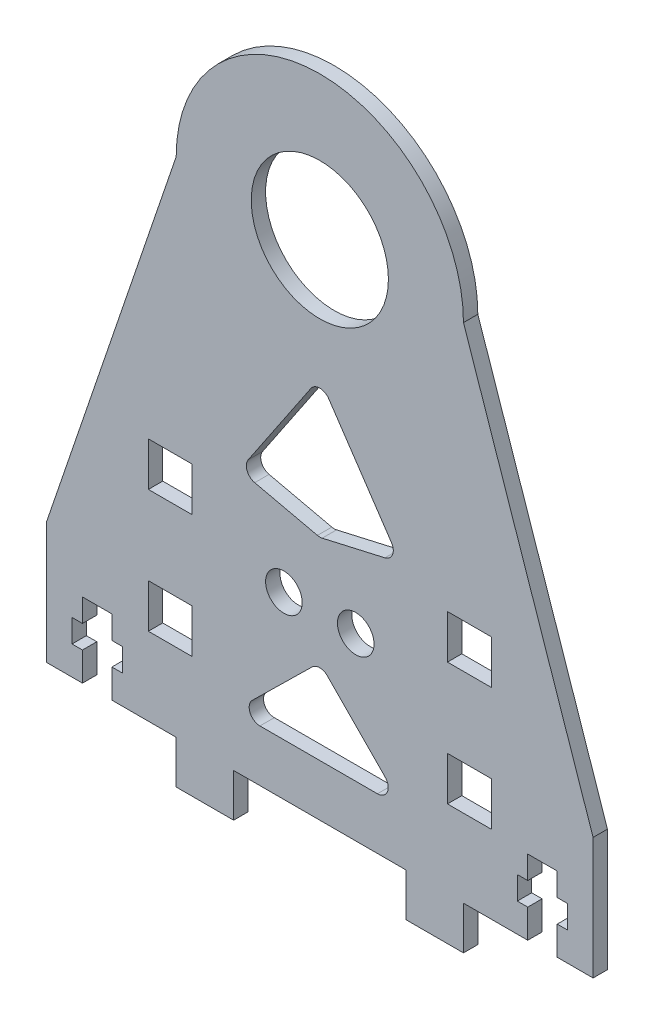
SolidWorks part; units mm, degrees
ref_plane "前视基准面" through (0, 0, 0) normal (0, 0, 1) x (1, 0, 0)
ref_plane "上视基准面" through (0, 0, 0) normal (0, 1, 0) x (1, 0, 0)
ref_plane "右视基准面" through (0, 0, 0) normal (1, 0, 0) x (0, 0, -1)
sketch "草图1" plane through (0, 0, 0) normal (0, 0, 1) x (1, 0, 0)
  line L0 (-30.7912, 3.1303) -> (31.2088, 3.1303) construction
  line L1 (-30.7912, 3.1303) -> (-30.7912, 5.1553) construction
  line L2 (-28.7412, 3.1303) -> (-28.7412, 7.1303)
  line L3 (-28.7412, 7.1303) -> (-27.2912, 7.1303)
  line L4 (-27.2912, 7.1303) -> (-27.2912, 10.3303)
  line L5 (-27.2912, 10.3303) -> (-28.7412, 10.3303)
  line L6 (-28.7412, 10.3303) -> (-28.7412, 13.5303)
  line L7 (-28.7412, 13.5303) -> (-32.8412, 13.5303)
  line L8 (-34.2912, 7.1303) -> (-34.2912, 10.3303)
  line L9 (-32.8412, 10.3303) -> (-32.8412, 13.5303)
  line L10 (-32.8412, 3.1303) -> (-32.8412, 7.1303)
  line L11 (-32.8412, 7.1303) -> (-34.2912, 7.1303)
  line L12 (-34.2912, 10.3303) -> (-32.8412, 10.3303)
  line L13 (-32.8412, 3.1303) -> (-37.8412, 3.1303)
  line L14 (-37.8412, 3.1303) -> (-37.8412, 93.1303) construction
  line L15 (-19.7912, 3.1303) -> (-19.7912, -2.8697)
  line L16 (-19.7912, -2.8697) -> (-11.7912, -2.8697)
  line L17 (-11.7912, -2.8697) -> (-11.7912, 3.1303)
  line L18 (-15.7912, -2.8697) -> (-15.7912, 3.1303) construction
  line L19 (-28.7412, 3.1303) -> (-19.7912, 3.1303)
  line L20 (0.2088, 3.1303) -> (0.2088, -7.8241) construction
  line L21 (-11.7912, 3.1303) -> (12.2088, 3.1303)
  line L22 (16.2088, -2.8697) -> (16.2088, 3.1303) construction
  line L23 (31.2088, 3.1303) -> (31.2088, 5.1553) construction
  line L24 (29.1588, 3.1303) -> (20.2088, 3.1303)
  line L25 (12.2088, -2.8697) -> (12.2088, 3.1303)
  line L26 (20.2088, -2.8697) -> (12.2088, -2.8697)
  line L27 (20.2088, 3.1303) -> (20.2088, -2.8697)
  line L28 (38.2588, 3.1303) -> (38.2588, 93.1303) construction
  line L29 (33.2588, 3.1303) -> (38.2588, 3.1303)
  line L30 (34.7088, 10.3303) -> (33.2588, 10.3303)
  line L31 (33.2588, 7.1303) -> (34.7088, 7.1303)
  line L32 (33.2588, 3.1303) -> (33.2588, 7.1303)
  line L33 (33.2588, 10.3303) -> (33.2588, 13.5303)
  line L34 (34.7088, 7.1303) -> (34.7088, 10.3303)
  line L35 (29.1588, 13.5303) -> (33.2588, 13.5303)
  line L36 (29.1588, 10.3303) -> (29.1588, 13.5303)
  line L37 (27.7088, 10.3303) -> (29.1588, 10.3303)
  line L38 (27.7088, 7.1303) -> (27.7088, 10.3303)
  line L39 (29.1588, 7.1303) -> (27.7088, 7.1303)
  line L40 (29.1588, 3.1303) -> (29.1588, 7.1303)
  line L41 (-37.8412, 93.1303) -> (38.2588, 93.1303) construction
  line L42 (0.2088, 3.1303) -> (0.2088, 73.1303) construction
  line L50 (-4.7912, 25.5803) -> (-34.2912, 25.5803) construction
  line L51 (-23.6625, 37.1803) -> (-17.5625, 37.1803)
  line L52 (-23.6625, 37.1803) -> (-23.6625, 31.0803)
  line L53 (-23.6625, 31.0803) -> (-17.5625, 31.0803)
  line L54 (-17.5625, 37.1803) -> (-17.5625, 31.0803)
  line L55 (-23.6625, 37.1803) -> (-17.5625, 31.0803) construction
  line L56 (-23.6625, 31.0803) -> (-17.5625, 37.1803) construction
  line L73 (-17.5625, 13.9803) -> (-17.5625, 20.0803)
  line L86 (-23.6625, 20.0803) -> (-17.5625, 20.0803)
  line L87 (-23.6625, 13.9803) -> (-23.6625, 20.0803)
  line L88 (-23.6625, 13.9803) -> (-17.5625, 13.9803)
  line L89 (-19.7912, 73.1303) -> (-37.8412, 20.0803)
  line L94 (0.2088, 22.1303) -> (-11.7912, 10.3303)
  line L95 (-11.7912, 10.3303) -> (11.8121, 10.3303)
  line L96 (11.8121, 10.3303) -> (0.2088, 22.1303)
  line L101 (-37.8412, 20.0803) -> (-37.8412, 3.1303)
  line L102 (24.0802, 31.0803) -> (17.9802, 31.0803)
  line L103 (17.9802, 37.1803) -> (17.9802, 31.0803)
  line L104 (24.0802, 37.1803) -> (24.0802, 31.0803)
  line L105 (24.0802, 37.1803) -> (17.9802, 37.1803)
  line L106 (24.0802, 20.0803) -> (17.9802, 20.0803)
  line L107 (24.0802, 13.9803) -> (24.0802, 20.0803)
  line L108 (17.9802, 13.9803) -> (17.9802, 20.0803)
  line L109 (24.0802, 13.9803) -> (17.9802, 13.9803)
  line L110 (38.2588, 20.0803) -> (38.2588, 3.1303)
  line L111 (20.2088, 73.1303) -> (38.2588, 20.0803)
  line L112 (-17.5625, 37.1803) -> (0.2088, 33.1303) construction
  line L113 (0.2088, 33.1303) -> (17.9802, 37.1803) construction
  line L114 (17.9802, 37.1803) -> (0.2088, 63.5803) construction
  line L115 (0.2088, 63.5803) -> (-17.5625, 37.1803) construction
  line L116 (0.2088, 56.4173) -> (-10.9877, 39.7845)
  line L117 (-10.9877, 39.7845) -> (0.2088, 37.2329)
  line L118 (0.2088, 37.2329) -> (11.4053, 39.7845)
  line L119 (11.4053, 39.7845) -> (0.2088, 56.4173)
  circle A0 centre (0.2088, 73.1303) radius 9.55
  circle A1 centre (0.2088, 73.1303) radius 40 construction
  circle A2 centre (-4.7912, 28.1303) radius 2.55
  circle A3 centre (5.2088, 28.1303) radius 2.55
  circle A6 centre (0.2088, 73.1303) radius 20 construction
  arc A7 (-19.7912, 73.1303) -> (20.2088, 73.1303) centre (0.2088, 73.1303) cw
  point P16 (-30.7912, 13.5303)
  point P47 (31.2088, 13.5303)
  point P55 (-20.6125, 34.1303)
  point P63 (-20.6125, 17.0303)
  dimension "D10" = 19.1
  dimension "D13" = 80
  dimension "D14" = 5.1
  dimension "D18" = 4
  dimension "D1" = 62
  dimension "D2" = 2.05
  dimension "D3" = 3.2
  dimension "D4" = 4
  dimension "D5" = 3.5
  dimension "D6" = 8
  dimension "D7" = 6
  dimension "D8" = 15
  dimension "D9" = 5
  dimension "D11" = 70
  dimension "D12" = 20
  dimension "D15" = 45
  dimension "D16" = 5
  dimension "D17" = 17.1
  dimension "D19" = 6.1
  dimension "D20" = 6.1
extrude "凸台-拉伸1" add sketch "草图1" along normal blind 2
sketch "草图2" plane through (0, 3.1303, 0) normal (0, -1, 0) x (1, 0, 0)
  line L0 (29.1588, 1) -> (33.2588, 1) construction
  line L1 (29.1588, 2) -> (29.1588, 0) construction
  line L2 (33.2588, 2) -> (33.2588, 0) construction
  circle A0 centre (31.2088, 1) radius 2.05
fillet "圆角3" radius 1.5 7 edges at (11.8121, 10.3303, 1) (-11.7912, 10.3303, 1) (0.2088, 22.1303, 1) (0.2088, 37.2329, 1) (11.4053, 39.7845, 1) (-10.9877, 39.7845, 1) (0.2088, 56.4173, 1)
